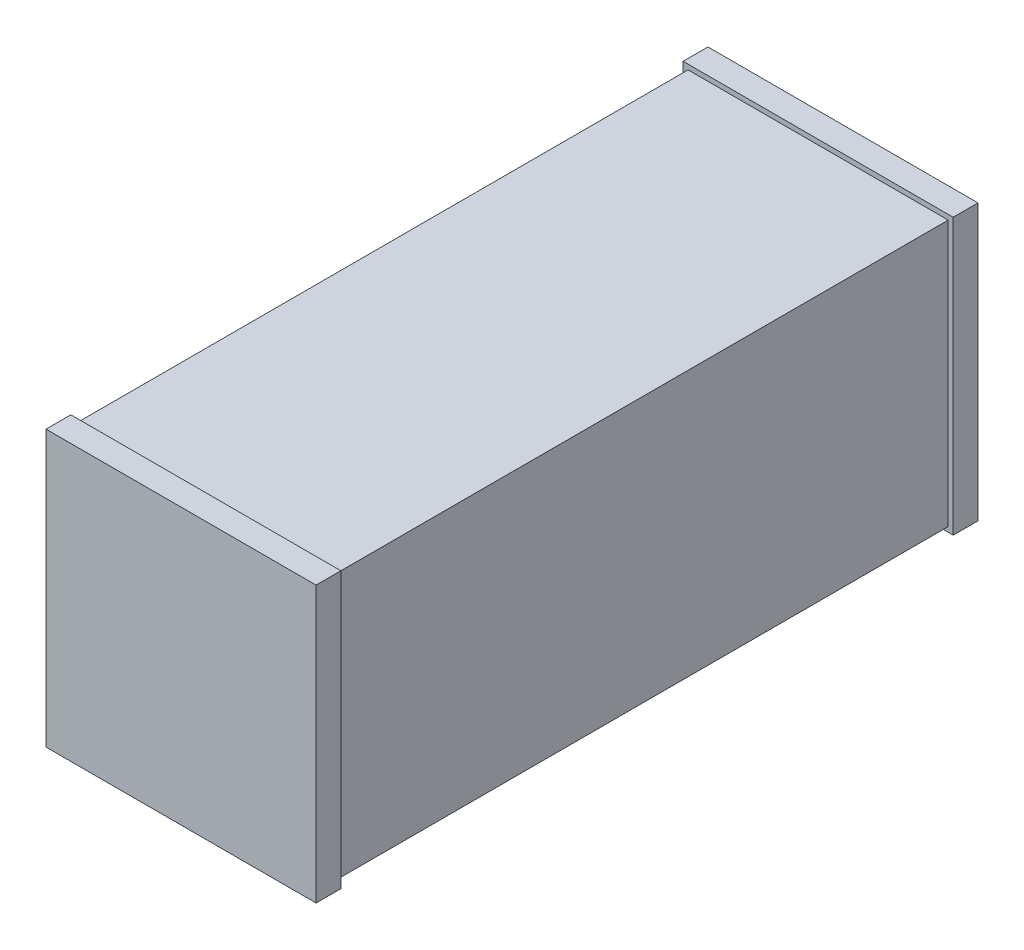
SolidWorks part; units mm, degrees
ref_plane "Front Plane" through (0, 0, 0) normal (0, 0, 1) x (1, 0, 0)
ref_plane "Top Plane" through (0, 0, 0) normal (0, 1, 0) x (1, 0, 0)
ref_plane "Right Plane" through (0, 0, 0) normal (1, 0, 0) x (0, 0, -1)
sketch "Sketch1" plane through (0, 0, 0) normal (0, 0, 1) x (1, 0, 0)
  line L1 (0, 0) -> (103.632, 0)
  line L2 (0, 0) -> (0, -105.664)
  line L3 (0, -105.664) -> (103.632, -105.664)
  line L4 (103.632, 0) -> (103.632, -105.664)
  dimension "D1" = 103.632
  dimension "D2" = 105.664
extrude "Boss-Extrude1" add sketch "Sketch1" against normal blind 9.525
sketch "Sketch2" plane through (0, 0, -9.525) normal (0, 0, -1) x (-1, 0, 0)
  line L0 (-103.632, 0) -> (0, 0) construction
  line L1 (-101.727, -1.905) -> (-1.905, -1.905)
  line L2 (-101.727, -1.905) -> (-101.727, -103.759)
  line L3 (-101.727, -103.759) -> (-1.905, -103.759)
  line L4 (-1.905, -1.905) -> (-1.905, -103.759)
  line L5 (-103.632, -105.664) -> (-103.632, 0) construction
  line L6 (0, 0) -> (0, -105.664) construction
  line L7 (0, -105.664) -> (-103.632, -105.664) construction
  dimension "D1" = 1.905
  dimension "D2" = 1.905
  dimension "D3" = 1.905
  dimension "D4" = 1.905
extrude "Boss-Extrude2" add sketch "Sketch2" along normal blind 234.95
sketch "Sketch4" plane through (0, 0, -244.475) normal (0, 0, -1) x (-1, 0, 0)
  line L8 (0, 0) -> (-103.632, 0)
  line L9 (-103.632, 0) -> (-103.632, -105.664)
  line L10 (-103.632, -105.664) -> (0, -105.664)
  line L11 (0, -105.664) -> (0, 0)
  line L12 (0, 0) -> (-103.632, 0)
  line L13 (-103.632, 0) -> (-103.632, -105.664)
  line L14 (-103.632, -105.664) -> (0, -105.664)
  line L15 (0, -105.664) -> (0, 0)
  dimension "D1" = 0
extrude "Boss-Extrude5" add sketch "Sketch4" along normal blind 9.525
sketch "Sketch5" plane through (0, -103.759, 0) normal (0, -1, 0) x (1, 0, 0)
  line L0 (101.727, -9.525) -> (1.905, -9.525) construction
  line L2 (15.3035, -19.05) -> (1.905, -19.05) construction
  line L3 (1.905, -244.475) -> (1.905, -9.525) construction
  line L4 (88.3285, -19.05) -> (101.727, -19.05) construction
  line L5 (101.727, -244.475) -> (101.727, -9.525) construction
  line L6 (15.3035, -234.95) -> (1.905, -234.95) construction
  line L7 (88.3285, -234.95) -> (101.727, -234.95) construction
  point P0 (15.3035, -19.05)
  point P1 (88.3285, -19.05)
  point P2 (15.3035, -234.95)
  point P3 (88.3285, -234.95)
  dimension "D1" = 73.025
  dimension "D2" = 215.9
  dimension "D3" = 9.525
hole_wizard "Tap Drill for #6-32 Tap1" positions "Sketch6" profile "Sketch7" hole size "#6-32" standard "ANSI Inch"
sketch "Sketch6" plane through (0, -103.759, 0) normal (0, -1, 0) x (-1, 0, 0)
  point P0 (-88.3285, 234.95)
  point P3 (-15.3035, 234.95)
  point P6 (-88.3285, 19.05)
  point P9 (-15.3035, 19.05)
sketch "Sketch7" plane through (88.3285, -103.759, -234.95) normal (1, 0, 0) x (0, 0, -1)
  line L0 (0, 0) -> (0, 4.7827)
  line L1 (0, 4.7827) -> (1.3525, 3.97)
  line L2 (1.3525, 3.97) -> (1.3525, 0)
  line L5 (1.3525, 0) -> (0, 0)
  line L10 (0, 4.7827) -> (-1.3526, 3.97) construction
  line L11 (0, -6.35) -> (0, 107.95) construction
  dimension "Hole Dia." = 2.7051
  dimension "Hole Depth" = 3.97
  dimension "Drill Angle" = 118
